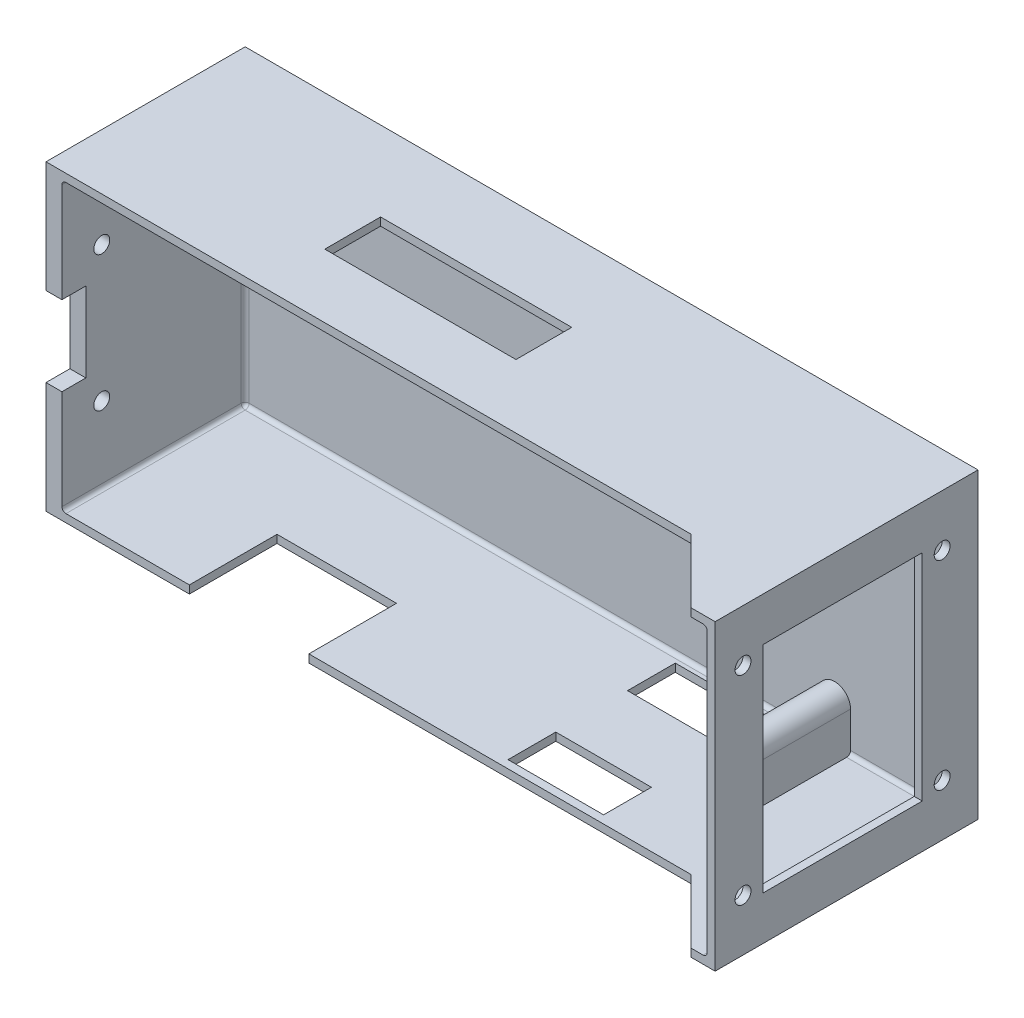
SolidWorks part; units mm, degrees
ref_plane "前视基准面" through (0, 0, 0) normal (0, 0, 1) x (1, 0, 0)
ref_plane "上视基准面" through (0, 0, 0) normal (0, 1, 0) x (1, 0, 0)
ref_plane "右视基准面" through (0, 0, 0) normal (1, 0, 0) x (0, 0, -1)
sketch "草图1" plane through (0, 0, 0) normal (0, 0, 1) x (1, 0, 0)
  line L1 (-45, 19) -> (45, 19)
  line L2 (-45, 19) -> (-45, -19)
  line L3 (-45, -19) -> (45, -19)
  line L4 (45, 19) -> (45, -19)
  line L5 (-45, 19) -> (45, -19) construction
  line L6 (-45, -19) -> (45, 19) construction
  point P0 (0, 0)
  dimension "D1" = 90
  dimension "D2" = 38
extrude "凸台-拉伸1" add sketch "草图1" along normal blind 2
sketch "草图2" plane through (0, 0, 2) normal (0, 0, 1) x (1, 0, 0)
  line L1 (44, 18) -> (-44, 18)
  line L3 (-44, -18) -> (44, -18)
  line L4 (45, -19) -> (45, 19)
  line L5 (45, 19) -> (-45, 19)
  line L6 (-45, 19) -> (-45, -19)
  line L7 (-45, -19) -> (45, -19)
  line L9 (45, 19) -> (-45, 19)
  line L11 (-45, -19) -> (45, -19)
  line L12 (44, -18) -> (44, 18) construction
  line L13 (45, -19) -> (45, 19) construction
  line L21 (-44, 18) -> (-45, 18)
  line L22 (-44, 18) -> (-44, -18) construction
  line L23 (-45, 19) -> (-45, -19) construction
  line L24 (-45, 19) -> (-45, -19) construction
  line L25 (-44, -18) -> (-45, -18)
  line L26 (-45, 18) -> (-45, 19)
  line L27 (-45, -18) -> (-45, -19)
  line L28 (44, -18) -> (44, 18)
  line L29 (45, 19) -> (45, -19)
  dimension "D1" = 0
  dimension "D2" = 1
extrude "凸台-拉伸2" add sketch "草图2" along normal blind 23
sketch "草图3" plane through (0, -19, 0) normal (0, -1, 0) x (1, 0, 0)
  line L0 (-45, 25) -> (-45, 0) construction
  line L1 (10, 9) -> (22, 9)
  line L2 (10, 9) -> (10, 3)
  line L3 (10, 3) -> (22, 3)
  line L4 (22, 9) -> (22, 3)
  line L5 (-45, 0) -> (45, 0) construction
  line L6 (-45, 25) -> (45, 25) construction
  line L7 (10, 24) -> (22, 24)
  line L8 (10, 24) -> (10, 18)
  line L9 (10, 18) -> (22, 18)
  line L10 (22, 24) -> (22, 18)
  line L12 (-29, 25) -> (-14, 25)
  line L13 (-29, 25) -> (-29, 14)
  line L14 (-29, 14) -> (-14, 14)
  line L15 (-14, 25) -> (-14, 14)
  dimension "D1" = 55
  dimension "D2" = 67
  dimension "D3" = 3
  dimension "D4" = 6
  dimension "D5" = 1
  dimension "D6" = 6
  dimension "D7" = 55
  dimension "D8" = 67
  dimension "D9" = 16
  dimension "D10" = 31
  dimension "D11" = 14
  dimension "D12" = 11
extrude "切除-拉伸1" cut sketch "草图3" against normal up to next
sketch "草图4" plane through (0, 19, 0) normal (0, 1, 0) x (1, 0, 0)
  line L0 (-45, -25) -> (-45, 0) construction
  line L1 (4, -17) -> (-20, -17)
  line L2 (4, -17) -> (4, -10)
  line L3 (4, -10) -> (-20, -10)
  line L4 (-20, -17) -> (-20, -10)
  line L5 (45, 0) -> (-45, 0) construction
  dimension "D1" = 25
  dimension "D2" = 24
  dimension "D3" = 7
  dimension "D4" = 10
extrude "切除-拉伸2" cut sketch "草图4" against normal up to next
sketch "草图7" plane through (0, 0, 25) normal (0, 0, 1) x (1, 0, 0)
  line L0 (-45, -19) -> (-29, -19) construction
  line L1 (45, 19) -> (44, 19)
  line L2 (45, 19) -> (45, -19)
  line L3 (45, -19) -> (44, -19)
  line L4 (44, 19) -> (44, -19)
  dimension "D1" = 1
extrude "凸台-拉伸3" add sketch "草图7" along normal blind 8
sketch "草图6" plane through (45, 0, 0) normal (1, 0, 0) x (0, 0, -1)
  line L0 (-17, -13.5) -> (-17, -19) construction
  line L1 (-27, 13.5) -> (-7, 13.5)
  line L2 (-27, 13.5) -> (-27, -13.5)
  line L3 (-27, -13.5) -> (-7, -13.5)
  line L4 (-7, 13.5) -> (-7, -13.5)
  line L5 (-33, -19) -> (0, -19) construction
  line L6 (-17, 13.5) -> (-17, 19) construction
  line L7 (-33, 19) -> (0, 19) construction
  line L8 (0, -19) -> (0, 19) construction
  line L9 (-31, -14.5) -> (-3, -14.5) construction
  line L10 (-31, -14.5) -> (-31, 14.5) construction
  line L11 (-31, 14.5) -> (-3, 14.5) construction
  line L12 (-3, -14.5) -> (-3, 14.5) construction
  point P16 (-17, 14.5)
  dimension "D1" = 20
  dimension "D2" = 27
  dimension "D3" = 29
  dimension "D4" = 28
  dimension "D5" = 1
  dimension "D6" = 3
extrude "切除-拉伸3" cut sketch "草图6" against normal up to next
sketch "草图8" plane through (45, 0, 0) normal (1, 0, 0) x (0, 0, -1)
  line L0 (-27, 13.5) -> (-27, -13.5) construction
  line L1 (-27, 13.5) -> (-7, 13.5) construction
  line L2 (-27, 13.5) -> (-27, -13.5) construction
  line L3 (-27, -13.5) -> (-7, -13.5) construction
  line L4 (-7, 13.5) -> (-7, -13.5) construction
  line L5 (-7, 13.5) -> (-27, 13.5) construction
  line L6 (-31, -14.5) -> (-3, -14.5) construction
  line L7 (-31, -14.5) -> (-31, 14.5) construction
  line L8 (-31, 14.5) -> (-3, 14.5) construction
  line L9 (-3, -14.5) -> (-3, 14.5) construction
  circle A0 centre (-29.5, 12.5) radius 1
  circle A1 centre (-29.5, -12.5) radius 1
  circle A2 centre (-4.5, -12.5) radius 1
  circle A3 centre (-4.5, 12.5) radius 1
  point P12 (-17, 14.5)
  dimension "D15" = 2
  dimension "D16" = 2
  dimension "D17" = 2
  dimension "D18" = 2
  dimension "D1" = 4
  dimension "D2" = 4
  dimension "D3" = 1
  dimension "D4" = 1
  dimension "D5" = 20
  dimension "D6" = 27
  dimension "D7" = 2
  dimension "D8" = 1.5
  dimension "D9" = 2
  dimension "D10" = 1.5
  dimension "D11" = 2
  dimension "D12" = 1.5
  dimension "D13" = 2
  dimension "D14" = 1.5
extrude "切除-拉伸4" cut sketch "草图8" against normal up to next
chamfer "倒角1" distance 10 angle 45 2 edges at (44, 18.5, 25) (44, -18.5, 25)
fillet "圆角1" radius 0.5 5 edges at (44, -18, 17.5) (44, 18, 17.5) (-0.5, -18, 2) (44, 0, 2) (-0.5, 18, 2)
sketch "草图10" plane through (0, 0, 2) normal (0, 0, 1) x (1, 0, 0)
  line L0 (-45, 17.5) -> (-45, -17.5) construction
  line L1 (-45, 0) -> (43.5, 0) construction
  line L2 (31, 13) -> (31, 18)
  line L3 (-45, 18) -> (34, 18) construction
  line L4 (27, 13) -> (27, 18)
  line L5 (43.5, -17.5) -> (43.5, 17.5) construction
  line L6 (31, -13) -> (31, -18)
  line L7 (27, -13) -> (27, -18)
  line L8 (31, 18) -> (27, 18)
  line L9 (31, -18) -> (27, -18)
  arc A1 (27, 13) -> (31, 13) centre (29, 13) ccw
  circle A2 centre (29, 13) radius 0.95
  circle A3 centre (29, -13) radius 0.95
  arc A4 (27, -13) -> (31, -13) centre (29, -13) cw
  dimension "D3" = 4
  dimension "D6" = 1.9
  dimension "D1" = 74
  dimension "D2" = 13
extrude "凸台-拉伸4" add sketch "草图10" along normal blind 11
sketch "草图11" plane through (-45, 0, 0) normal (-1, 0, 0) x (0, 0, 1)
  line L0 (12.5, 10.5) -> (12.5, 19) construction
  line L1 (0, 19) -> (25, 19)
  line L2 (0, 19) -> (0, -19)
  line L3 (0, -19) -> (25, -19)
  line L4 (25, 19) -> (25, 5)
  line L5 (22, 10.5) -> (3, 10.5) construction
  line L6 (22, 10.5) -> (22, -10.5) construction
  line L7 (22, -10.5) -> (3, -10.5) construction
  line L8 (3, 10.5) -> (3, -10.5) construction
  line L9 (12.5, -10.5) -> (12.5, -19) construction
  line L10 (3, 0) -> (0, 0) construction
  line L12 (25, -5) -> (25, -19)
  line L13 (25, 5) -> (22, 5)
  line L15 (25, -5) -> (22, -5)
  line L16 (22, 5) -> (22, -5)
  circle A0 centre (20, 8.5) radius 1
  circle A1 centre (20, -8.5) radius 1
  point P27 (0, 0)
  dimension "D3" = 2
  dimension "D4" = 2
  dimension "D1" = 21
  dimension "D2" = 19
  dimension "D5" = 2
  dimension "D6" = 2
  dimension "D7" = 2
  dimension "D8" = 2
  dimension "D9" = 3
  dimension "D10" = 10
  dimension "D11" = 14
extrude "凸台-拉伸5" add sketch "草图11" along normal blind 2
fillet "圆角2" radius 0.5 5 edges at (-45, -18, 13.75) (-45, -17.8536, 2.1464) (-45, 0, 2) (-45, 17.8536, 2.1464) (-45, 18, 13.75)
